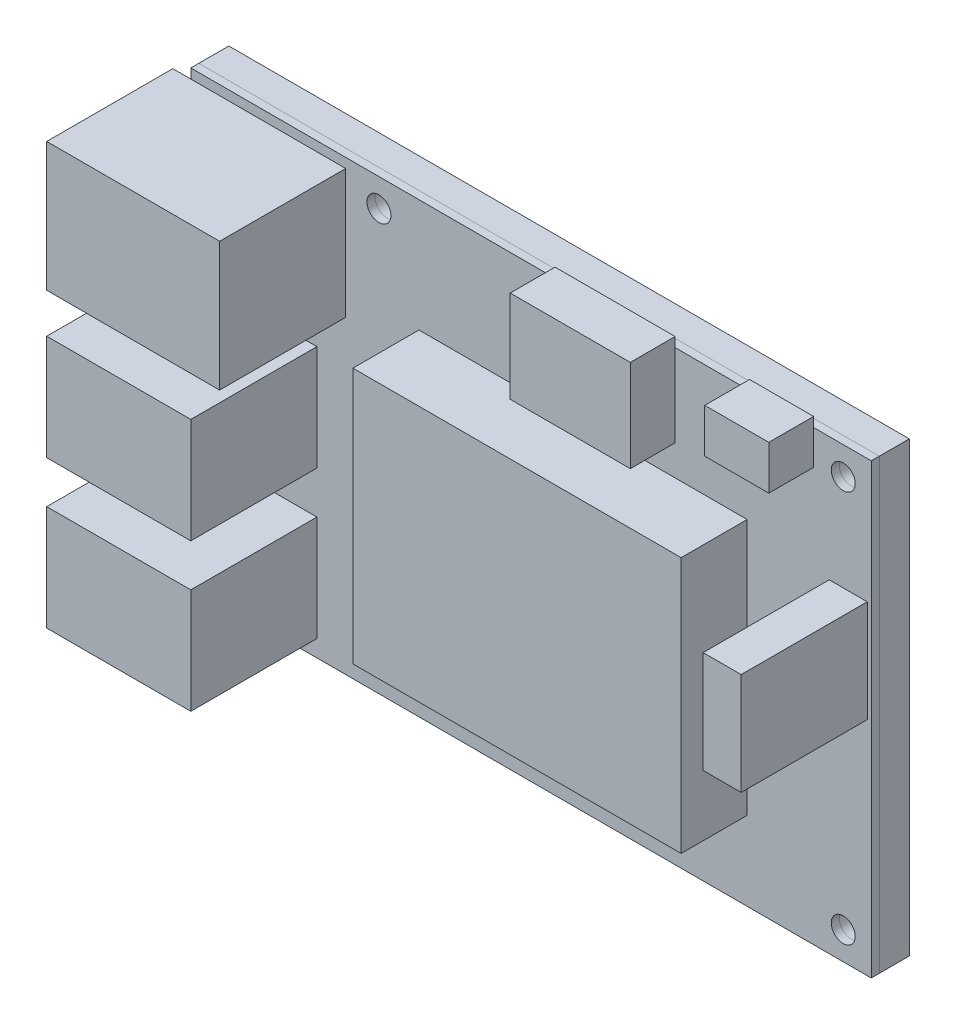
SolidWorks part; units mm, degrees
ref_plane "Front Plane" through (0, 0, 0) normal (0, 0, 1) x (1, 0, 0)
ref_plane "Top Plane" through (0, 0, 0) normal (0, 1, 0) x (1, 0, 0)
ref_plane "Right Plane" through (0, 0, 0) normal (1, 0, 0) x (0, 0, -1)
sketch "Sketch1" plane through (0, 0, 0) normal (0, 0, 1) x (1, 0, 0)
  line L0 (-19, 24.5) -> (39, 24.5) construction
  line L1 (-42.5, 27.975) -> (42.5, 27.975)
  line L2 (-42.5, 27.975) -> (-42.5, -27.975)
  line L3 (-42.5, -27.975) -> (42.5, -27.975)
  line L4 (42.5, 27.975) -> (42.5, -27.975)
  line L5 (39, 24.5) -> (39, -24.5) construction
  line L6 (39, -24.5) -> (-19, -24.5) construction
  line L7 (-19, -24.5) -> (-19, 24.5) construction
  line L8 (39, 0) -> (42.5, 0) construction
  line L9 (55, 0) -> (-55, 0) construction
  line L10 (0, -55) -> (0, 55) construction
  circle A0 centre (-19, 24.5) radius 1.5
  circle A1 centre (-19, -24.5) radius 1.5
  circle A2 centre (39, 24.5) radius 1.5
  circle A3 centre (39, -24.5) radius 1.5
  point P12 (-19, 0)
  point P17 (0, 27.975)
  dimension "D1" = 3
  dimension "D2" = 58
  dimension "D3" = 49
  dimension "D4" = 55.95
  dimension "D5" = 85
  dimension "D6" = 3.5
extrude "Boss-Extrude1" add sketch "Sketch1" along normal blind 1
extrude "Boss-Extrude2-lower-keepout" add sketch "Sketch1<2>" against normal blind 3.75 separate body
sketch "Sketch1<2>" plane through (0, 0, 0) normal (0, 0, 1) x (1, 0, 0) same geometry as "Sketch1"
sketch "Sketch3" plane through (0, 0, 1) normal (0, 0, 1) x (1, 0, 0)
  line L0 (42.5, 27.975) -> (42.5, -27.975) construction
  line L1 (-14, 13.875) -> (27, 13.875)
  line L2 (-14, 13.875) -> (-14, -18.125)
  line L3 (-14, -18.125) -> (27, -18.125)
  line L4 (27, 13.875) -> (27, -18.125)
  line L5 (-42.5, 27.975) -> (42.5, 27.975) construction
  dimension "D1" = 41
  dimension "D2" = 32
  dimension "D3" = 15.5
  dimension "D4" = 14.1
extrude "Boss-Extrude3" add sketch "Sketch3" along normal blind 8.25
sketch "Sketch4" plane through (0, 0, 1) normal (0, 0, 1) x (1, 0, 0)
  line L0 (-44.7495, -0.865) -> (-34.7495, -0.865) construction
  line L1 (-44.7495, 5.705) -> (-26.7495, 5.705)
  line L2 (-44.7495, 5.705) -> (-44.7495, -7.435)
  line L3 (-44.7495, -7.435) -> (-26.7495, -7.435)
  line L4 (-26.7495, 5.705) -> (-26.7495, -7.435)
  line L5 (-44.7495, -12.735) -> (-26.7495, -12.735)
  line L6 (-44.7495, -12.735) -> (-44.7495, -25.875)
  line L7 (-44.7495, -25.875) -> (-26.7495, -25.875)
  line L8 (-26.7495, -12.735) -> (-26.7495, -25.875)
  line L9 (-44.7495, -19.305) -> (-34.7495, -19.305) construction
  line L10 (42.5, -27.975) -> (42.5, 27.975) construction
  line L11 (37.245, 12.475) -> (42, 12.475)
  line L12 (-44.7495, 26.775) -> (-23.1495, 26.775)
  line L13 (-44.7495, 26.775) -> (-44.7495, 10.675)
  line L14 (-44.7495, 10.675) -> (-23.1495, 10.675)
  line L15 (-23.1495, 26.775) -> (-23.1495, 10.675)
  line L16 (37.245, 12.475) -> (37.245, -0.275)
  line L17 (37.245, -0.275) -> (42, -0.275)
  line L18 (42, 12.475) -> (42, -0.275)
  line L19 (42.5, 27.975) -> (-42.5, 27.975) construction
  dimension "D1" = 18
  dimension "D2" = 13.14
  dimension "D3" = 10
  dimension "D4" = 5.3
  dimension "D5" = 2.1
  dimension "D6" = 21.6
  dimension "D7" = 1.2
  dimension "D8" = 16.1
  dimension "D9" = 4.755
  dimension "D10" = 12.75
  dimension "D11" = 0.5
  dimension "D12" = 15.5
extrude "Boss-Extrude4" add sketch "Sketch4" along normal blind 15.75
sketch "Sketch5" plane through (0, 0, 1) normal (0, 0, 1) x (1, 0, 0)
  line L1 (3, 29.175) -> (18, 29.175)
  line L2 (3, 29.175) -> (3, 17.675)
  line L3 (3, 17.675) -> (18, 17.675)
  line L4 (18, 29.175) -> (18, 17.675)
  line L5 (27.3, 29.175) -> (35.3, 29.175)
  line L6 (27.3, 29.175) -> (27.3, 23.675)
  line L7 (27.3, 23.675) -> (35.3, 23.675)
  line L8 (35.3, 29.175) -> (35.3, 23.675)
  dimension "D1" = 15
  dimension "D2" = 8
  dimension "D3" = 11.5
  dimension "D4" = 5.5
  dimension "D5" = 1.2
  dimension "D6" = 24.5
  dimension "D7" = 7.2
extrude "Boss-Extrude5" add sketch "Sketch5" along normal blind 5.6
sketch "Sketch6" plane through (0, 0, 0) normal (0, 0, 1) x (1, 0, 0)
  line L0 (-42.5, -27.975) -> (42.5, -27.975) construction
  line L1 (-0.5969, -28.475) -> (-12.2069, -28.475)
  line L2 (-0.5969, -28.475) -> (-0.5969, -12.725)
  line L3 (-0.5969, -12.725) -> (-12.2069, -12.725)
  line L4 (-12.2069, -28.475) -> (-12.2069, -12.725)
  dimension "D1" = 11.61
  dimension "D2" = 15.75
  dimension "D3" = 0.5
extrude "Boss-Extrude6" add sketch "Sketch6" against normal blind 4 separate body
